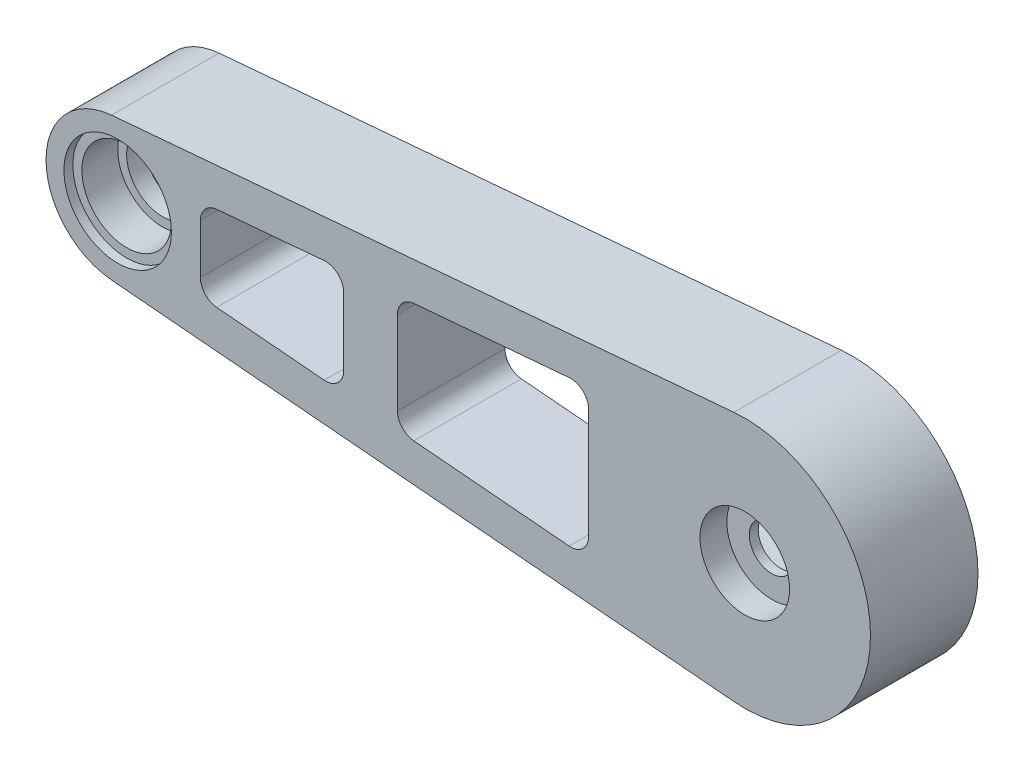
SolidWorks part; units mm, degrees
ref_plane "前视基准面" through (0, 0, 0) normal (0, 0, 1) x (1, 0, 0)
ref_plane "上视基准面" through (0, 0, 0) normal (0, 1, 0) x (1, 0, 0)
ref_plane "右视基准面" through (0, 0, 0) normal (1, 0, 0) x (0, 0, -1)
sketch "草图2" plane through (0, 0, 0) normal (0, 0, 1) x (1, 0, 0)
  line L1 (-35.3448, 3.9851) -> (-0.6048, 6.9905)
  line L2 (-35.3448, -3.9851) -> (-0.6048, -6.9905)
  arc A0 (-0.6048, -6.9905) -> (-0.6048, 6.9905) centre (0, 0) ccw
  arc A2 (-35.3448, 3.9851) -> (-35.3448, -3.9851) centre (-35, 0) ccw
  dimension "D1" = 35
  dimension "D3" = 8
extrude "凸台-拉伸1" add sketch "草图2" along normal blind 6
sketch "草图6" plane through (0, 0, 6) normal (0, 0, 1) x (1, 0, 0)
  line L0 (-30.386, 2.2911) -> (-22.386, 2.9832)
  line L1 (-19.386, 3.2427) -> (-19.386, -3.2427)
  line L2 (-0.6048, 6.9905) -> (-35.3448, 3.9851) construction
  line L3 (-19.386, 3.2427) -> (-8.7157, 4.1659)
  line L4 (-30.386, -2.2911) -> (-22.386, -2.9832)
  line L5 (-35.3448, -3.9851) -> (-0.6048, -6.9905) construction
  line L6 (-8.7157, 4.1659) -> (-8.7157, -4.1659)
  line L7 (-30.386, 2.2911) -> (-30.386, -2.2911)
  line L8 (-22.386, 2.9832) -> (-22.386, -2.9832)
  line L10 (-19.386, -3.2427) -> (-8.7157, -4.1659)
  dimension "D1" = 8
  dimension "D2" = 3
extrude "切除-拉伸1" cut sketch "草图6" against normal through all
fillet "圆角1" radius 1 8 edges at (-8.7157, -4.1659, 3) (-8.7157, 4.1659, 3) (-19.386, -3.2427, 3) (-19.386, 3.2427, 3) (-22.386, -2.9832, 3) (-22.386, 2.9832, 3) (-30.386, -2.2911, 3) (-30.386, 2.2911, 3)
sketch "草图7" plane through (0, 0, 6) normal (0, 0, 1) x (1, 0, 0)
  circle A1 centre (-35, 0) radius 2.5
  circle A2 centre (-35, 0) radius 3
  circle A3 centre (-35, 0) radius 2
  dimension "D1" = 5
  dimension "D3" = 6
  dimension "D4" = 4
extrude "切除-拉伸2" cut sketch "草图7" against normal through all contours A3 region at (-35, 0, 6)
extrude "切除-拉伸4" cut sketch "草图7<4>" against normal blind 2.5 contours A1 A3 region at (-37.4293, 0, 6)
sketch "草图7<4>" plane through (0, 0, 6) normal (0, 0, 1) x (1, 0, 0) same geometry as "草图7"
extrude "切除-拉伸5" cut sketch "草图7<5>" against normal blind 0.5 contours A2 A1 region at (-37.9151, 0, 6)
sketch "草图7<5>" plane through (0, 0, 6) normal (0, 0, 1) x (1, 0, 0) same geometry as "草图7"
sketch "草图8" plane through (0, 0, 6) normal (0, 0, 1) x (1, 0, 0)
  line L1 (-12.25, 1.9843) -> (-0.4375, 3.4725)
  line L2 (-12.25, -1.9843) -> (-0.4375, -3.4725)
  arc A0 (-0.4375, -3.4725) -> (-0.4375, 3.4725) centre (0, 0) ccw
  arc A1 (-12.25, 1.9843) -> (-12.25, -1.9843) centre (-12, 0) ccw
  dimension "D1" = 7
  dimension "D3" = 4
  dimension "D2" = 12
sketch "草图12" plane through (0, 0, 0) normal (0, 0, -1) x (-1, 0, 0)
  line L0 (12.25, 1.9843) -> (0.4375, 3.4725)
  line L1 (12.25, -1.9843) -> (0.4375, -3.4725)
  arc A0 (0.4375, 3.4725) -> (0.4375, -3.4725) centre (0, 0) ccw
  arc A1 (12.25, -1.9843) -> (12.25, 1.9843) centre (12, 0) ccw
extrude "切除-拉伸9" cut sketch "草图12" against normal blind 4
sketch "草图13" plane through (0, 0, 4) normal (0, 0, -1) x (-1, 0, 0)
  circle A0 centre (0, 0) radius 1.25
  dimension "D1" = 2.5
extrude "切除-拉伸10" cut sketch "草图13" against normal through all
sketch "草图14" plane through (0, 0, 6) normal (0, 0, 1) x (1, 0, 0)
  circle A0 centre (0, 0) radius 2.5
  dimension "D1" = 5
extrude "切除-拉伸11" cut sketch "草图14" against normal blind 1.5
sketch "草图15" plane through (0, 0, 0) normal (0, 0, -1) x (-1, 0, 0)
  circle A0 centre (35, 0) radius 2.5
  circle A1 centre (35, 0) radius 3
  dimension "D1" = 6
  dimension "D2" = 5
extrude "切除-拉伸13" cut sketch "草图15" against normal blind 2.5 contours A0
extrude "切除-拉伸14" cut sketch "草图15<4>" against normal blind 0.5
sketch "草图15<4>" plane through (0, 0, 0) normal (0, 0, -1) x (-1, 0, 0) same geometry as "草图15"
